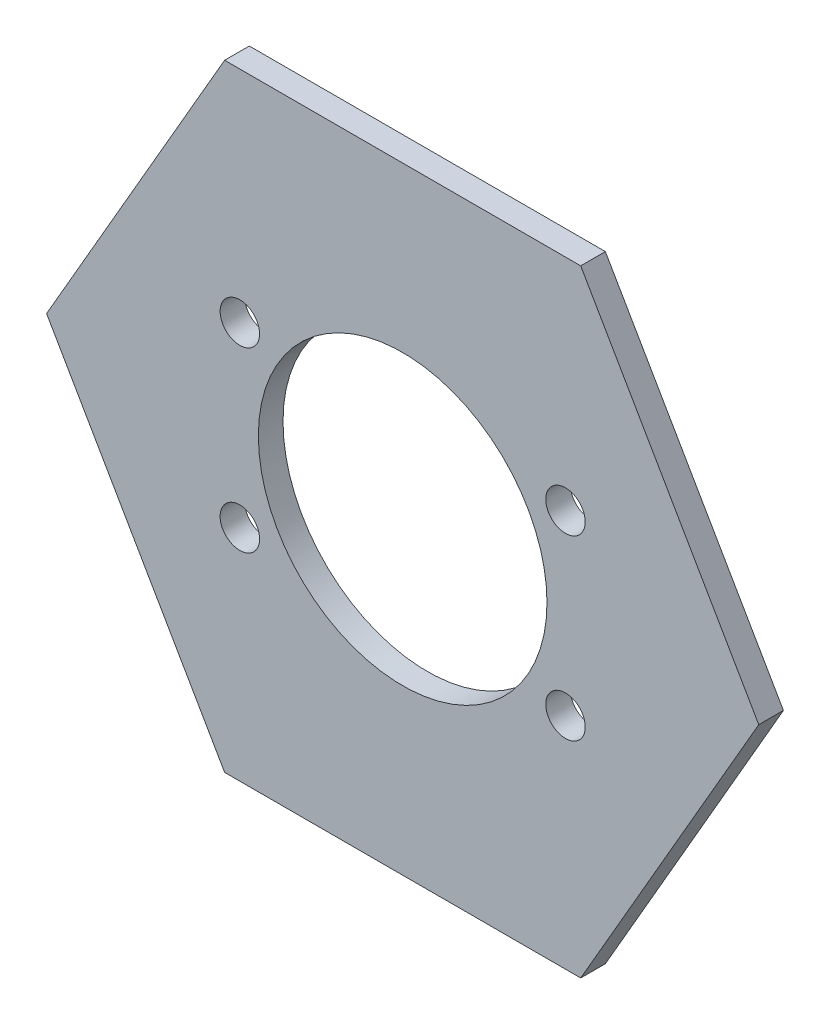
SolidWorks part; units mm, degrees
ref_plane "Front Plane" through (0, 0, 0) normal (0, 0, 1) x (1, 0, 0)
ref_plane "Top Plane" through (0, 0, 0) normal (0, 1, 0) x (1, 0, 0)
ref_plane "Right Plane" through (0, 0, 0) normal (1, 0, 0) x (0, 0, -1)
sketch "Sketch1" plane through (0, 0, 0) normal (0, 0, 1) x (1, 0, 0)
  line L0 (0, 0) -> (0, -25) construction
  line L1 (-5, -17.5) -> (5, -17.5) construction
  line L2 (-14.4338, 25) -> (14.4338, 25)
  line L3 (-5, -19) -> (5, -19) construction
  line L4 (-5, -19) -> (-5, -24) construction
  line L5 (-5, -24) -> (5, -24) construction
  line L6 (5, -19) -> (5, -24) construction
  line L7 (14.4338, 25) -> (28.8675, 0)
  line L8 (28.8675, 0) -> (14.4338, -25)
  line L9 (14.4338, -25) -> (-14.4338, -25)
  line L10 (-14.4338, -25) -> (-28.8675, 0)
  line L11 (-28.8675, 0) -> (-14.4338, 25)
  circle A0 centre (0, 0) radius 8 construction
  circle A1 centre (0, 0) radius 11.7
  circle A2 centre (0, 0) radius 11.2 construction
  circle A3 centre (0, 0) radius 11.2 construction
  circle A6 centre (-13.2, -7.2) radius 1.6
  circle A7 centre (-13.2, 7.2) radius 1.6
  circle A8 centre (13.2, 7.2) radius 1.6
  circle A9 centre (13.2, -7.2) radius 1.6
  circle A10 centre (0, 0) radius 25 construction
  circle A11 centre (-13.2, -7.2) radius 1.6 construction
  circle A12 centre (-13.2, 7.2) radius 1.6 construction
  circle A13 centre (13.2, 7.2) radius 1.6 construction
  circle A14 centre (13.2, -7.2) radius 1.6 construction
  dimension "D2" = 50
  dimension "D1" = 0.5
  dimension "D3" = 5
  dimension "D4" = 10
  dimension "D5" = 1
extrude "Boss-Extrude1" add sketch "Sketch1" along normal blind 2
sketch "Sketch2" plane through (0, 0, 0) normal (0, 0, 1) x (1, 0, 0)
  line L0 (-39.2529, 1.012) -> (-31.4586, -3.488) construction
  line L1 (-39.6189, 2.378) -> (-36.2439, 8.2237) construction
  line L2 (-27.9497, 4.5897) -> (-34.8779, 8.5897) construction
  line L3 (-17.4006, 19.8612) -> (-25.9006, 5.1388) construction
  line L4 (-17.9497, 21.9103) -> (-24.8779, 25.9103) construction
  line L5 (-21.8689, 33.122) -> (-25.2439, 27.2763) construction
  line L6 (-20.5029, 33.488) -> (-12.7086, 28.988) construction
  line L7 (20.5029, 33.488) -> (12.7086, 28.988) construction
  line L8 (21.8689, 33.122) -> (25.2439, 27.2763) construction
  line L9 (17.9497, 21.9103) -> (24.8779, 25.9103) construction
  line L10 (17.4006, 19.8612) -> (25.9006, 5.1388) construction
  line L11 (27.9497, 4.5897) -> (34.8779, 8.5897) construction
  line L12 (39.6189, 2.378) -> (36.2439, 8.2237) construction
  line L13 (39.2529, 1.012) -> (31.4586, -3.488) construction
  line L14 (18.75, -34.5) -> (18.75, -25.5) construction
  line L15 (17.75, -35.5) -> (11, -35.5) construction
  line L16 (10, -34.5) -> (10, -22.5) construction
  line L17 (5, -17.5) -> (-5, -17.5) construction
  line L18 (-10, -34.5) -> (-10, -22.5) construction
  line L19 (-17.75, -35.5) -> (-11, -35.5) construction
  line L20 (-18.75, -34.5) -> (-18.75, -25.5) construction
  line L21 (-39.2529, 1.012) -> (-31.4586, -3.488)
  line L22 (-39.6189, 2.378) -> (-36.2439, 8.2237)
  line L23 (-27.9497, 4.5897) -> (-34.8779, 8.5897)
  line L24 (-17.4006, 19.8612) -> (-25.9006, 5.1388)
  line L25 (-17.9497, 21.9103) -> (-24.8779, 25.9103)
  line L26 (-21.8689, 33.122) -> (-25.2439, 27.2763)
  line L27 (-20.5029, 33.488) -> (-12.7086, 28.988)
  line L28 (20.5029, 33.488) -> (12.7086, 28.988)
  line L29 (21.8689, 33.122) -> (25.2439, 27.2763)
  line L30 (17.9497, 21.9103) -> (24.8779, 25.9103)
  line L31 (17.4006, 19.8612) -> (25.9006, 5.1388)
  line L32 (27.9497, 4.5897) -> (34.8779, 8.5897)
  line L33 (39.6189, 2.378) -> (36.2439, 8.2237)
  line L34 (39.2529, 1.012) -> (31.4586, -3.488)
  line L35 (18.75, -34.5) -> (18.75, -25.5)
  line L36 (17.75, -35.5) -> (11, -35.5)
  line L37 (10, -34.5) -> (10, -22.5)
  line L38 (5, -17.5) -> (-5, -17.5)
  line L39 (-10, -34.5) -> (-10, -22.5)
  line L40 (-17.75, -35.5) -> (-11, -35.5)
  line L41 (-18.75, -34.5) -> (-18.75, -25.5)
  arc A0 (-18.75, -25.5) -> (-31.4586, -3.488) centre (-44.1673, -25.5) ccw construction
  arc A1 (-39.6189, 2.378) -> (-39.2529, 1.012) centre (-38.7529, 1.878) ccw construction
  arc A2 (-34.8779, 8.5897) -> (-36.2439, 8.2237) centre (-35.3779, 7.7237) ccw construction
  arc A3 (-27.9497, 4.5897) -> (-25.9006, 5.1388) centre (-27.1997, 5.8888) ccw construction
  arc A4 (-17.4006, 19.8612) -> (-17.9497, 21.9103) centre (-18.6997, 20.6112) ccw construction
  arc A5 (-25.2439, 27.2763) -> (-24.8779, 25.9103) centre (-24.3779, 26.7763) ccw construction
  arc A6 (-20.5029, 33.488) -> (-21.8689, 33.122) centre (-21.0029, 32.622) ccw construction
  arc A7 (-12.7086, 28.988) -> (12.7086, 28.988) centre (0, 51) ccw construction
  arc A8 (21.8689, 33.122) -> (20.5029, 33.488) centre (21.0029, 32.622) ccw construction
  arc A9 (24.8779, 25.9103) -> (25.2439, 27.2763) centre (24.3779, 26.7763) ccw construction
  arc A10 (17.9497, 21.9103) -> (17.4006, 19.8612) centre (18.6997, 20.6112) ccw construction
  arc A11 (25.9006, 5.1388) -> (27.9497, 4.5897) centre (27.1997, 5.8888) ccw construction
  arc A12 (36.2439, 8.2237) -> (34.8779, 8.5897) centre (35.3779, 7.7237) ccw construction
  arc A13 (39.2529, 1.012) -> (39.6189, 2.378) centre (38.7529, 1.878) ccw construction
  arc A14 (31.4586, -3.488) -> (18.75, -25.5) centre (44.1673, -25.5) ccw construction
  arc A15 (17.75, -35.5) -> (18.75, -34.5) centre (17.75, -34.5) ccw construction
  arc A16 (10, -34.5) -> (11, -35.5) centre (11, -34.5) ccw construction
  arc A17 (10, -22.5) -> (5, -17.5) centre (5, -22.5) ccw construction
  arc A18 (-5, -17.5) -> (-10, -22.5) centre (-5, -22.5) ccw construction
  arc A19 (-11, -35.5) -> (-10, -34.5) centre (-11, -34.5) ccw construction
  arc A20 (-18.75, -34.5) -> (-17.75, -35.5) centre (-17.75, -34.5) ccw construction
  arc A21 (-18.75, -25.5) -> (-31.4586, -3.488) centre (-44.1673, -25.5) ccw
  arc A22 (-39.6189, 2.378) -> (-39.2529, 1.012) centre (-38.7529, 1.878) ccw
  arc A23 (-34.8779, 8.5897) -> (-36.2439, 8.2237) centre (-35.3779, 7.7237) ccw
  arc A24 (-27.9497, 4.5897) -> (-25.9006, 5.1388) centre (-27.1997, 5.8888) ccw
  arc A25 (-17.4006, 19.8612) -> (-17.9497, 21.9103) centre (-18.6997, 20.6112) ccw
  arc A26 (-25.2439, 27.2763) -> (-24.8779, 25.9103) centre (-24.3779, 26.7763) ccw
  arc A27 (-20.5029, 33.488) -> (-21.8689, 33.122) centre (-21.0029, 32.622) ccw
  arc A28 (-12.7086, 28.988) -> (12.7086, 28.988) centre (0, 51) ccw
  arc A29 (21.8689, 33.122) -> (20.5029, 33.488) centre (21.0029, 32.622) ccw
  arc A30 (24.8779, 25.9103) -> (25.2439, 27.2763) centre (24.3779, 26.7763) ccw
  arc A31 (17.9497, 21.9103) -> (17.4006, 19.8612) centre (18.6997, 20.6112) ccw
  arc A32 (25.9006, 5.1388) -> (27.9497, 4.5897) centre (27.1997, 5.8888) ccw
  arc A33 (36.2439, 8.2237) -> (34.8779, 8.5897) centre (35.3779, 7.7237) ccw
  arc A34 (39.2529, 1.012) -> (39.6189, 2.378) centre (38.7529, 1.878) ccw
  arc A35 (31.4586, -3.488) -> (18.75, -25.5) centre (44.1673, -25.5) ccw
  arc A36 (17.75, -35.5) -> (18.75, -34.5) centre (17.75, -34.5) ccw
  arc A37 (10, -34.5) -> (11, -35.5) centre (11, -34.5) ccw
  arc A38 (10, -22.5) -> (5, -17.5) centre (5, -22.5) ccw
  arc A39 (-5, -17.5) -> (-10, -22.5) centre (-5, -22.5) ccw
  arc A40 (-11, -35.5) -> (-10, -34.5) centre (-11, -34.5) ccw
  arc A41 (-18.75, -34.5) -> (-17.75, -35.5) centre (-17.75, -34.5) ccw
